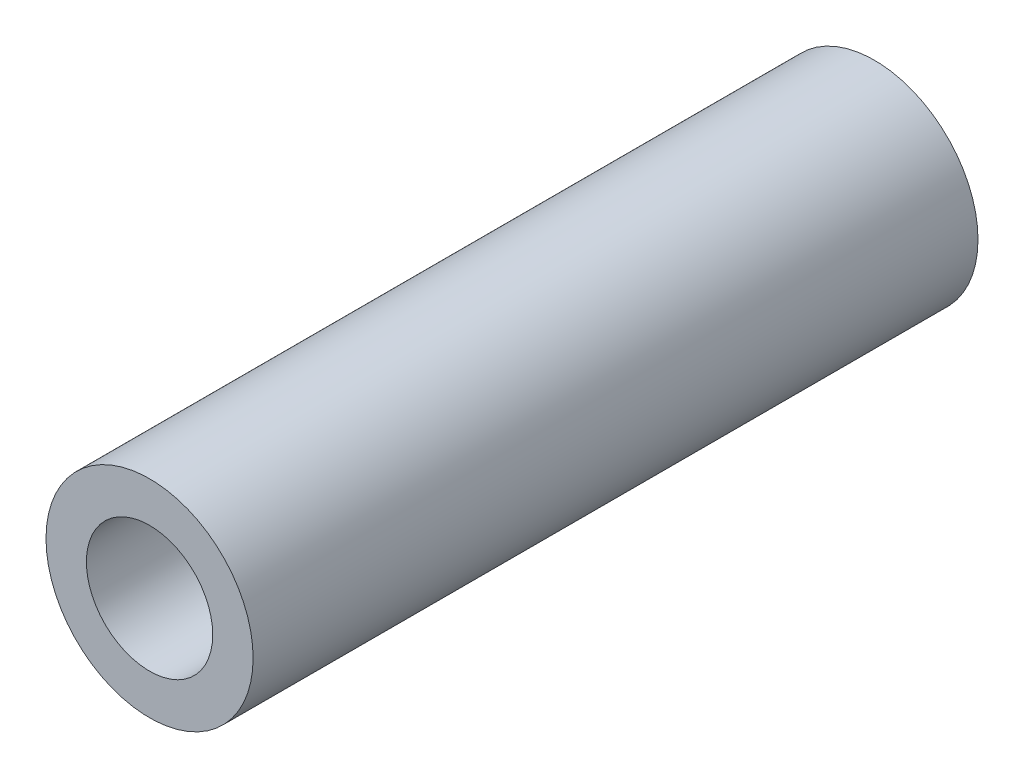
SolidWorks part; units mm, degrees
ref_plane "Front Plane" through (0, 0, 0) normal (0, 0, 1) x (1, 0, 0)
ref_plane "Top Plane" through (0, 0, 0) normal (0, 1, 0) x (1, 0, 0)
ref_plane "Right Plane" through (0, 0, 0) normal (1, 0, 0) x (0, 0, -1)
sketch "Sketch2" plane through (0, 0, 0) normal (0, 0, 1) x (1, 0, 0)
  circle A0 centre (0, 0) radius 10
  circle A1 centre (0, 0) radius 6.1
  dimension "D1" = 20
  dimension "D2" = 12.2
extrude "Boss-Extrude1" add sketch "Sketch2" along normal blind 25
sketch "Sketch3" plane through (0, 0, 25) normal (0, 0, 1) x (1, 0, 0)
  circle A0 centre (0, 0) radius 10
  dimension "D1" = 20
extrude "Boss-Extrude2" add sketch "Sketch3" along normal blind 45
sketch "Sketch4" plane through (0, 0, 70) normal (0, 0, 1) x (1, 0, 0)
  circle A0 centre (0, 0) radius 6.1
  dimension "D1" = 12.2
extrude "Cut-Extrude1" cut sketch "Sketch4" against normal blind 45
